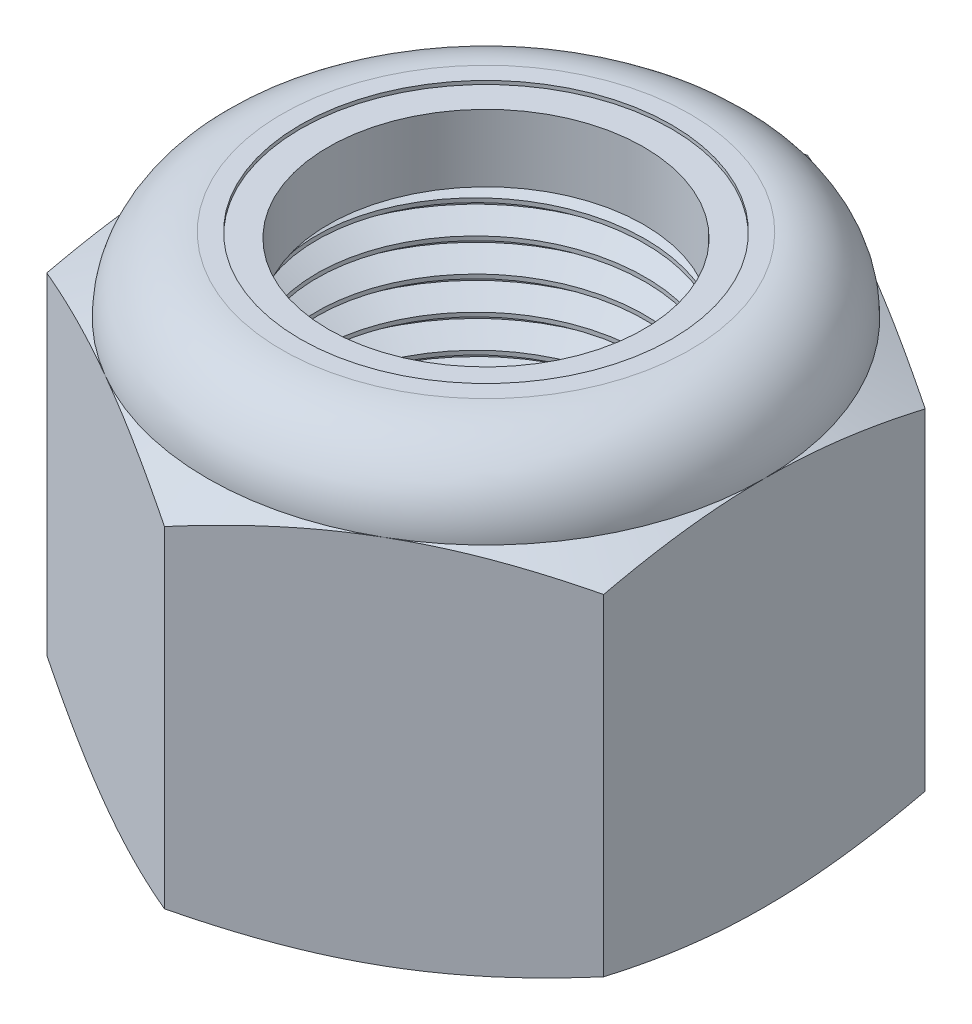
SolidWorks part; units mm, degrees
note: '?' marks a value the reader was unsure of.
ref_plane "Front" through (0, 0, 0) normal (0, 0, 1) x (1, 0, 0)
ref_plane "Top" through (0, 0, 0) normal (0, 1, 0) x (1, 0, 0)
ref_plane "Right" through (0, 0, 0) normal (1, 0, 0) x (0, 0, -1)
sketch "Sketch8" plane through (0, 0, 0) normal (1, 0, 0) x (0, 0, -1)
  line L0 (0, 0) -> (0, 19.05) construction
  line L1 (11.9062, 0) -> (-11.9062, 0) construction
  line L2 (-7.9375, 19.05) -> (7.9375, 19.05) construction
  line L3 (7.9375, 19.05) -> (7.9375, 17.6389) construction
sketch "Sketch1" plane through (0, 0, 0) normal (0, 1, 0) x (1, 0, 0)
  line L1 (0, 13.7482) -> (-11.9062, 6.8741)
  line L2 (-11.9062, 6.8741) -> (-11.9062, -6.8741)
  line L3 (-11.9062, -6.8741) -> (0, -13.7482)
  line L4 (0, -13.7482) -> (11.9063, -6.8741)
  line L5 (11.9063, -6.8741) -> (11.9063, 6.8741)
  line L6 (11.9063, 6.8741) -> (0, 13.7482)
  circle A0 centre (0, 0) radius 11.9062 construction
  circle A1 centre (0, 0) radius 7.9375
extrude "Extrude1" add sketch "Sketch1" along normal up to vertex (19.05 mm away) up to point (0, 19.05, 0)
sketch "Sketch5" plane through (0, 0, 0) normal (1, 0, 0) x (0, 0, -1)
  line L0 (0, 0) -> (11.9062, 0)
  line L1 (11.9062, 0) -> (13.7482, 0.8589)
  line L2 (13.7482, 0.8589) -> (13.7482, 15.0161)
  line L3 (13.7482, 15.0161) -> (11.9062, 15.875)
  line L4 (8.7312, 19.05) -> (8.7312, 20.32)
  line L5 (8.7312, 20.32) -> (15.0182, 20.32)
  line L6 (15.0182, 20.32) -> (15.0182, -1.27)
  line L7 (15.0182, -1.27) -> (0, -1.27)
  line L8 (0, -1.27) -> (0, 0)
  line L9 (11.9062, 15.875) -> (11.9062, 0) construction
  line L12 (13.7482, 19.05) -> (13.7482, 0) construction
  line L13 (13.7482, 9.525) -> (15.0182, 9.525) construction
  line L15 (0, 0) -> (0, 20.32) construction
  line L18 (11.9062, 0) -> (-11.9062, 0) construction
  line L19 (6.8741, 19.05) -> (13.7482, 19.05) construction
  line L20 (0, 20.32) -> (8.7312, 20.32) construction
  line L21 (6.8741, 0) -> (13.7482, 0) construction
  arc A0 (11.9062, 15.875) -> (8.7312, 19.05) centre (8.7312, 15.875) ccw
  dimension "D1" = 25
  dimension "D2" = 1.27
  dimension "D4" = 3.175
revolve "Cut-Revolve3" cut sketch "Sketch5" angle 360 about L15
sketch "Sketch4" plane through (0, 0, 0) normal (1, 0, 0) x (0, 0, -1)
  line L0 (0, 15.875) -> (8.7312, 15.875)
  line L1 (8.7312, 15.875) -> (0, 11.8036)
  line L3 (0, 4.0714) -> (8.7312, 0)
  line L4 (8.7312, 0) -> (0, 0)
  line L5 (0, 0) -> (0, 15.875) construction
  line L10 (0, 0) -> (0, 19.05) construction
  line L11 (0, 4.0714) -> (0, 0)
  line L12 (0, 15.875) -> (0, 11.8036)
  line L13 (10.3111, 15.875) -> (0, 15.875) construction
  dimension "D1" = 25
  dimension "D2" = 17.4625
sketch "Sketch6" plane through (0, 0, 0) normal (1, 0, 0) x (0, 0, -1)
  line L0 (0, 15.875) -> (11.7538, 15.875)
  line L1 (8.7312, 18.8976) -> (4.3656, 18.8976)
  line L2 (0, 20.32) -> (0, 15.875)
  line L3 (4.3656, 20.32) -> (0, 20.32)
  line L4 (0, 20.32) -> (8.7312, 20.32) construction
  line L5 (0, 0) -> (0, 20.32) construction
  line L6 (0, 20.32) -> (0, 0) construction
  line L7 (4.3656, 18.8976) -> (4.3656, 20.32)
  line L8 (8.7312, 19.05) -> (8.7312, 18.8976) construction
  line L9 (4.3656, 18.8976) -> (0, 18.8976) construction
  line L10 (0, 18.8976) -> (0, 11.8036) construction
  arc A0 (11.7538, 15.875) -> (8.7312, 18.8976) centre (8.7312, 15.875) ccw
  arc A1 (11.9062, 15.875) -> (8.7312, 19.05) centre (8.7312, 15.875) ccw construction
  dimension "D1" = 0.1524
revolve "Cut-Revolve4" cut sketch "Sketch6" angle 360 about L6
revolve "Cut-Revolve2" cut sketch "Sketch4" angle 360 about L5
sketch "Sketch7" plane through (0, 0, 0) normal (1, 0, 0) x (0, 0, -1)
  line L0 (6.7469, 15.9512) -> (11.6767, 15.9512)
  line L1 (8.7312, 18.8214) -> (6.7469, 18.8214)
  line L2 (6.7469, 18.8214) -> (6.7469, 15.9512)
  line L3 (6.7469, 15.9512) -> (0, 15.9512) construction
  line L4 (0, 15.9512) -> (0, 18.8214) construction
  line L5 (0, 18.8214) -> (6.7469, 18.8214) construction
  line L6 (6.7469, 15.9512) -> (6.7469, 15.875) construction
  line L7 (0, 15.875) -> (11.7538, 15.875) construction
  line L8 (8.7312, 18.8214) -> (8.7312, 18.8976) construction
  arc A0 (11.6767, 15.9512) -> (8.7312, 18.8214) centre (8.7312, 15.875) ccw
  arc A2 (11.7538, 15.875) -> (8.7312, 18.8976) centre (8.7312, 15.875) ccw construction
  dimension "D1" = 0.0762
  dimension "D2" = 13.4937
revolve "Revolve2" add sketch "Sketch7" angle 360 about L4
sketch "Sketch2" plane through (0, 0, 0) normal (1, 0, 0) x (0, 0, -1)
  line L0 (-7.9375, 0) -> (-7.9375, 15.875) construction
  line L1 (0, 0) -> (7.9375, 0)
  line L2 (0, 0) -> (0, 15.875)
  line L3 (0, 15.875) -> (7.9375, 15.875)
  line L4 (7.9375, 0) -> (7.9375, 15.875)
  line L6 (10.3111, 15.875) -> (11.9062, 15.875) construction
  line L7 (0, -7.9375) -> (0, 0) construction
revolve "Revolve1" add sketch "Sketch2" angle 360 about L7
sketch "Sketch9" plane through (0, 0, 0) normal (1, 0, 0) x (0, 0, -1)
  line L0 (8.0903, 17.1979) -> (8.0903, 15.7868) construction
  line L1 (8.0903, 15.7868) -> (6.8682, 16.4924) construction
  line L2 (6.8682, 16.4924) -> (8.0903, 17.1979) construction
  line L3 (7.021, 16.5806) -> (7.021, 16.4042) construction
  line L4 (7.9375, 17.1097) -> (7.9375, 15.875) construction
  line L5 (6.8682, 16.4924) -> (7.021, 16.4924) construction
  line L6 (7.9375, 16.4924) -> (8.0903, 16.4924) construction
  line L7 (8.0139, 16.4924) -> (8.0139, 17.1538) construction
  line L8 (8.0903, 15.7868) -> (8.0139, 17.1538)
  line L9 (8.0139, 17.1538) -> (7.021, 16.5806)
  line L10 (7.021, 16.5806) -> (7.021, 16.4042)
  line L11 (7.021, 16.4042) -> (8.0903, 15.7868)
  dimension "D1" = 1.4111
  dimension "D2" = 0.1764
sketch "Sketch10" plane through (0, 15.875, 0) normal (0, 1, 0) x (1, 0, 0)
  circle A1 centre (0, 0) radius 7.9375
  circle A2 centre (0, 0) radius 7.9375
  dimension "D1" = 0
curve "Helix/Spiral1" pitch 1.4111 height 20.4611 turns 14.5
sweep "Cut-Sweep1" cut profiles "Sketch9" path "Helix/Spiral1" align with end faces yes
sketch "Sketch11" plane through (0, 0, 0) normal (1, 0, 0) x (0, 0, -1)
  line L0 (0, 0) -> (0, 19.05) construction
  line L1 (11.9062, 0) -> (-11.9062, 0) construction
  line L4 (0, 19.05) -> (0, 0) construction
  line L5 (0, 9.525) -> (7.9375, 9.525) construction
  line L6 (0, 0) -> (8.7312, 0)
  line L7 (0, 4.0714) -> (0, 0)
  line L8 (8.7312, 0) -> (0, 4.0714)
  dimension "D1" = 17.4625
  dimension "D2" = 25
revolve "Revolve3" add sketch "Sketch11" angle 360 about L4
sketch "Sketch12" plane through (0, 0, 0) normal (1, 0, 0) x (0, 0, -1)
  line L0 (8.7312, 15.875) -> (0, 15.875)
  line L1 (0, 15.875) -> (0, 0)
  line L2 (0, 0) -> (8.7312, 0)
  line L3 (11.9062, 0) -> (-11.9062, 0) construction
  line L4 (8.7312, 0) -> (8.7312, 15.875)
  line L5 (-8.7312, 0) -> (8.7312, 0) construction
revolve "Revolve4" add sketch "Sketch12" angle 360 about L0
combine bodies "Combine1" operation type subtract main body 136 bodies to subtract 133
ref_plane "Contact Plane 1" through (0, 0, 0) normal (0, -1, 0) x (1, 0, 0)
ref_axis "Center Axis 1" through (0, -2.1015, 0) along (0, 1, 0)?
equation "\"D4@Sketch5\"=\"Height@Sketch8\"/6"
equation "\"D1@Sketch9\"=\"Thread Pitch@Sketch8\""
equation "\"D2@Sketch9\"=\"Thread Pitch@Sketch8\"/8"
equation "\"D4@Helix/Spiral1\"=\"Thread Pitch@Sketch8\""
equation "\"D3@Helix/Spiral1\"=\"Thread Pitch@Sketch8\"+\"Height@Sketch8\""
equation "\"D2@Sketch4\"=\"Thread Dia@Sketch8\"*1.1"
equation "\"D1@Sketch11\"=\"Thread Dia@Sketch8\"*1.1"
equation "\"D2@Sketch7\"=\"Thread Dia@Sketch8\"*.85"
